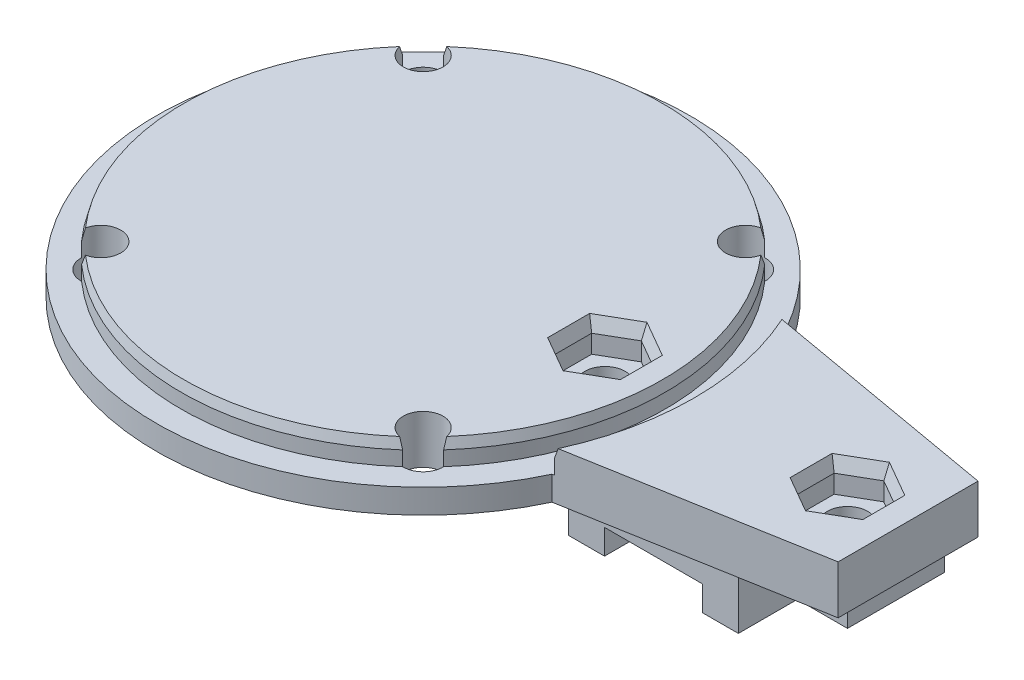
SolidWorks part; units mm, degrees
ref_plane "Спереди" through (0, 0, 0) normal (0, 0, 1) x (1, 0, 0)
ref_plane "Сверху" through (0, 0, 0) normal (0, 1, 0) x (1, 0, 0)
ref_plane "Справа" through (0, 0, 0) normal (1, 0, 0) x (0, 0, -1)
sketch "Эскиз1" plane through (0, 0, 0) normal (0, 1, 0) x (1, 0, 0)
  circle A0 centre (0, 0) radius 55
  dimension "D1" = 110
extrude "Бобышка-Вытянуть1" add sketch "Эскиз1" along normal blind 5
sketch "Эскиз2" plane through (0, 5, 0) normal (0, 1, 0) x (1, 0, 0)
  circle A0 centre (0, 0) radius 49.9
  dimension "D1" = 99.8
extrude "Бобышка-Вытянуть2" add sketch "Эскиз2" along normal blind 5
sketch "Sketch7" plane through (0, 0, 0) normal (0, -1, 0) x (1, 0, 0)
  line L0 (0, 0) -> (100, 0) construction
  line L2 (48.9898, -25) -> (100, -25)
  line L3 (48.9898, -25) -> (48.9898, 25)
  line L4 (48.9898, 25) -> (100, 25)
  line L5 (100, -25) -> (100, 25)
  line L6 (48.9898, -25) -> (100, 25) construction
  line L7 (48.9898, 25) -> (100, -25) construction
  circle A1 centre (0, 0) radius 55 construction
  point P3 (74.4949, 0)
  point P8 (100, 0)
  dimension "D1" = 100
  dimension "D2" = 50
extrude "Boss-Extrude2" add sketch "Sketch7" against normal up to surface (5 mm away) up to face at (0, 5, 49.9)
sketch "Эскиз3" plane through (0, 0, 0) normal (0, -1, 0) x (1, 0, 0)
  line L0 (-55, 0) -> (100, 0) construction
  line L1 (80, -15) -> (45, -15)
  line L2 (80, -15) -> (80, 15)
  line L3 (80, 15) -> (45, 15)
  line L4 (45, -15) -> (45, 15)
  line L5 (80, -15) -> (45, 15) construction
  line L6 (80, 15) -> (45, -15) construction
  line L7 (100, -25) -> (100, 25) construction
  arc A0 (48.9898, 25) -> (48.9898, -25) centre (0, 0) ccw construction
  point P0 (62.5, 0)
  dimension "D1" = 35
  dimension "D2" = 30
  dimension "D3" = 20
extrude "Бобышка-Вытянуть3" add sketch "Эскиз3" along normal blind 25
sketch "Эскиз4" plane through (0, 0, 15) normal (0, 0, 1) x (1, 0, 0)
  line L0 (45, 0) -> (80, -25) construction
  line L2 (72.6, -17.65) -> (52.4, -17.65)
  line L3 (72.6, -17.65) -> (72.6, -7.35)
  line L4 (72.6, -7.35) -> (52.4, -7.35)
  line L5 (52.4, -17.65) -> (52.4, -7.35)
  line L6 (72.6, -17.65) -> (52.4, -7.35) construction
  line L7 (72.6, -7.35) -> (52.4, -17.65) construction
  point P4 (62.5, -12.5)
  dimension "D1" = 20.2
  dimension "D2" = 10.3
extrude "Вырез-Вытянуть1" cut sketch "Эскиз4" against normal through all
sketch "Эскиз5" plane through (0, 0, 0) normal (0, -1, 0) x (1, 0, 0)
  line L1 (-33.234, -33.234) -> (33.234, -33.234) construction
  line L2 (-33.234, -33.234) -> (-33.234, 33.234) construction
  line L3 (-33.234, 33.234) -> (33.234, 33.234) construction
  line L4 (33.234, -33.234) -> (33.234, 33.234) construction
  line L5 (-33.234, -33.234) -> (33.234, 33.234) construction
  line L6 (-33.234, 33.234) -> (33.234, -33.234) construction
  circle A0 centre (0, 0) radius 55 construction
  circle A1 centre (33.234, -33.234) radius 4.1
  circle A2 centre (-33.234, -33.234) radius 4.1
  circle A3 centre (-33.234, 33.234) radius 4.1
  circle A4 centre (33.234, 33.234) radius 4.1
  circle A5 centre (0, 0) radius 47 construction
  point P0 (0, 0)
  dimension "D3" = 8.2
  dimension "D8" = 8
extrude "Вырез-Вытянуть2" cut sketch "Эскиз5" against normal through all
chamfer "Chamfer1" distance 2 angle 15 4 edges at (0, 10, 49.9) (-49.9, 10, 0) (0, 10, -49.9) (49.9, 10, 0) first distance on face at (0, 7.5, 43.6161) first distance on face at (-43.6161, 7.5, 0) first distance on face at (0, 7.5, -43.6161) first distance on face at (43.6161, 7.5, 0)
sketch "Sketch2" plane through (0, -25, 0) normal (0, -1, 0) x (1, 0, 0)
  line L0 (80, 0) -> (45, 0) construction
  line L1 (80, -15) -> (80, 15) construction
  line L2 (45, 15) -> (45, -15) construction
  line L4 (45, -15) -> (80, -15)
  line L5 (45, -15) -> (45, 15)
  line L6 (45, 15) -> (80, 15)
  line L7 (80, -15) -> (80, 15)
  line L8 (45, -15) -> (80, 15) construction
  line L9 (45, 15) -> (80, -15) construction
  point P6 (62.5, 0)
extrude "Cut-Extrude1" cut sketch "Sketch2" against normal blind 12.5
sketch "Sketch4" plane through (0, -7.35, 0) normal (0, -1, 0) x (1, 0, 0)
  line L0 (239.0884, 0) -> (0, 0) construction
  line L1 (27.5, -10) -> (97.5, -10)
  line L2 (27.5, -10) -> (27.5, 10)
  line L3 (27.5, 10) -> (97.5, 10)
  line L4 (97.5, -10) -> (97.5, 10)
  line L5 (27.5, -10) -> (97.5, 10) construction
  line L6 (27.5, 10) -> (97.5, -10) construction
  line L7 (62.5, -15) -> (62.5, 15) construction
  line L8 (72.6, -15) -> (52.4, -15) construction
  line L9 (72.6, 15) -> (52.4, 15) construction
  point P0 (62.5, 0)
  dimension "D1" = 20
  dimension "D2" = 70
extrude "Boss-Extrude1" add sketch "Sketch4" against normal up to surface (7.35 mm away) from offset 2 up to face at (-33.234, 0, -37.334) offset against normal yes
sketch "Sketch5" plane through (0, -5.35, 0) normal (0, -1, 0) x (1, 0, 0)
  line L0 (87.5, 10) -> (87.5, -10) construction
  line L1 (97.5, 10) -> (80, 10) construction
  line L2 (80, -10) -> (97.5, -10) construction
  line L3 (37.5, 10) -> (37.5, -10) construction
  line L4 (45, 10) -> (27.5, 10) construction
  line L5 (27.5, -10) -> (45, -10) construction
  line L6 (87.5, 0) -> (37.5, 0) construction
  line L7 (45, 0) -> (80, 0) construction
  line L8 (45, -10) -> (45, 10) construction
  line L9 (80, 10) -> (80, -10) construction
  circle A0 centre (87.5, 0) radius 4.15
  circle A1 centre (37.5, 0) radius 4.15
  point P21 (62.5, 0)
  point P23 (62.5, 0)
  dimension "D1" = 8.3
  dimension "D2" = 50
extrude "Cut-Extrude2" cut sketch "Sketch5" against normal through all
sketch "Sketch9" plane through (0, 5, 0) normal (0, 1, 0) x (1, 0, 0)
  line L0 (100, -25) -> (48.9898, -25) construction
  line L1 (48.9898, 25) -> (100, 25) construction
  line L2 (49.3898, -25) -> (100, -25)
  line L3 (100, -25) -> (100, 25)
  line L4 (100, 25) -> (49.3898, 25)
  arc A0 (49.3898, -25) -> (49.3898, 25) centre (0, 0) ccw
  arc A1 (48.9898, 25) -> (48.9898, -25) centre (0, 0) ccw construction
  circle A3 centre (37.5, 0) radius 4.15
  circle A4 centre (87.5, 0) radius 4.15
  dimension "D1" = 0.4
extrude "Boss-Extrude3" add sketch "Sketch9" along normal up to surface (5 mm away) up to face at (41.65, 10, 0)
chamfer "Chamfer3" distance 2 angle 15 1 edges at (55.3566, 10, 0) first distance on face at (52.3732, 7.5, 0)
sketch "Sketch6" plane through (0, 10, 0) normal (0, 1, 0) x (1, 0, 0)
  line L1 (43.9952, 3.75) -> (37.5, 7.5)
  line L2 (37.5, 7.5) -> (31.0048, 3.75)
  line L3 (31.0048, 3.75) -> (31.0048, -3.75)
  line L4 (31.0048, -3.75) -> (37.5, -7.5)
  line L5 (37.5, -7.5) -> (43.9952, -3.75)
  line L6 (43.9952, -3.75) -> (43.9952, 3.75)
  line L7 (93.9952, 3.75) -> (87.5, 7.5)
  line L8 (87.5, 7.5) -> (81.0048, 3.75)
  line L9 (81.0048, 3.75) -> (81.0048, -3.75)
  line L10 (81.0048, -3.75) -> (87.5, -7.5)
  line L11 (87.5, -7.5) -> (93.9952, -3.75)
  line L12 (93.9952, -3.75) -> (93.9952, 3.75)
  circle A0 centre (37.5, 0) radius 7.5 construction
  circle A1 centre (87.5, 0) radius 7.5 construction
  dimension "D1" = 15
extrude "Cut-Extrude3" cut sketch "Sketch6" against normal blind 6.5
chamfer "Chamfer2" distance 1 angle 70 12 edges at (34.2524, 10, -5.625) (31.0048, 10, 0) (34.2524, 10, 5.625) (40.7476, 10, 5.625) (43.9952, 10, 0) (40.7476, 10, -5.625) (90.7476, 10, 5.625) (93.9952, 10, 0) (90.7476, 10, -5.625) (84.2524, 10, -5.625) (81.0048, 10, 0) (84.2524, 10, 5.625) first distance on face at (37.5, 10, 0) first distance on face at (87.5, 10, 0)
chamfer "Chamfer4" distance 60 angle 10 2 edges at (100, 5, -25) (100, 5, 25) first distance on face at (63.7784, 5.2857, -25) first distance on face at (63.8641, 5.5714, 25)
